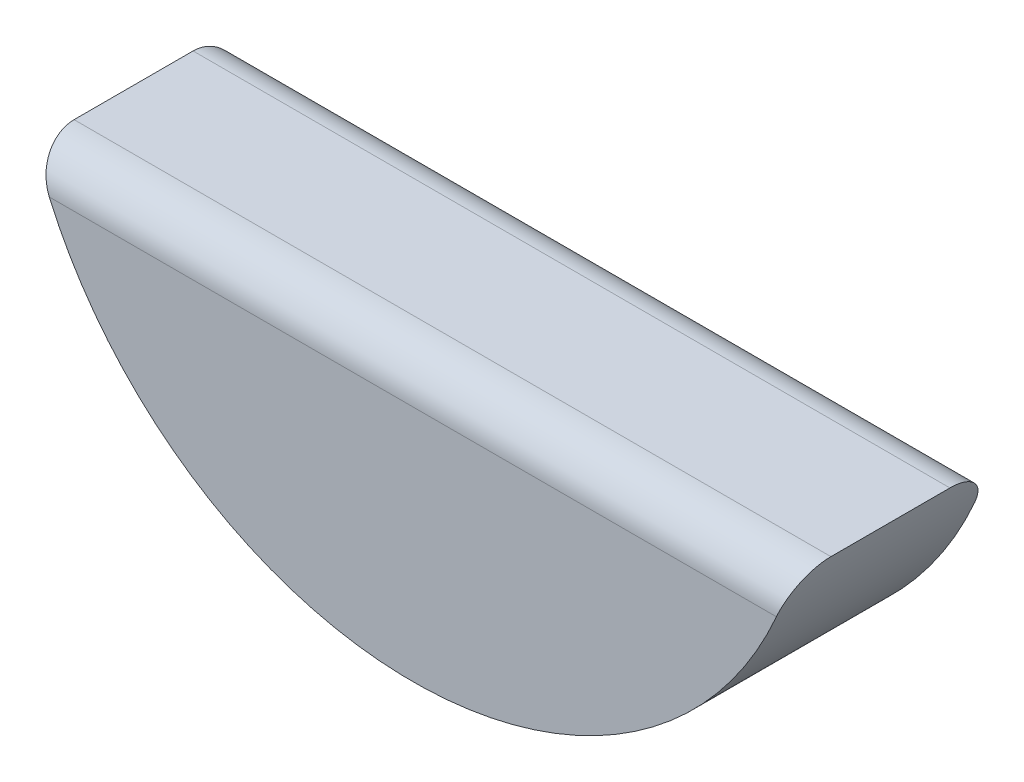
SolidWorks part; units mm, degrees
ref_plane "Front" through (0, 0, 0) normal (0, 0, 1) x (1, 0, 0)
ref_plane "Top" through (0, 0, 0) normal (0, 1, 0) x (1, 0, 0)
ref_plane "Right" through (0, 0, 0) normal (1, 0, 0) x (0, 0, -1)
sketch "Sketch1" plane through (0, 0, 0) normal (0, 0, 1) x (1, 0, 0)
  line L0 (-1.9079, 0) -> (1.9079, 0)
  arc A0 (-1.9079, 0) -> (1.9079, 0) centre (0, 0.6) ccw
  dimension "d2" = 4
  dimension "h" = 1.4
extrude "Extrude1" add sketch "Sketch1" along normal mid plane 1
fillet "Fillet1" radius 0.2 2 edges at (0, 0, -0.5) (0, 0, 0.5)
